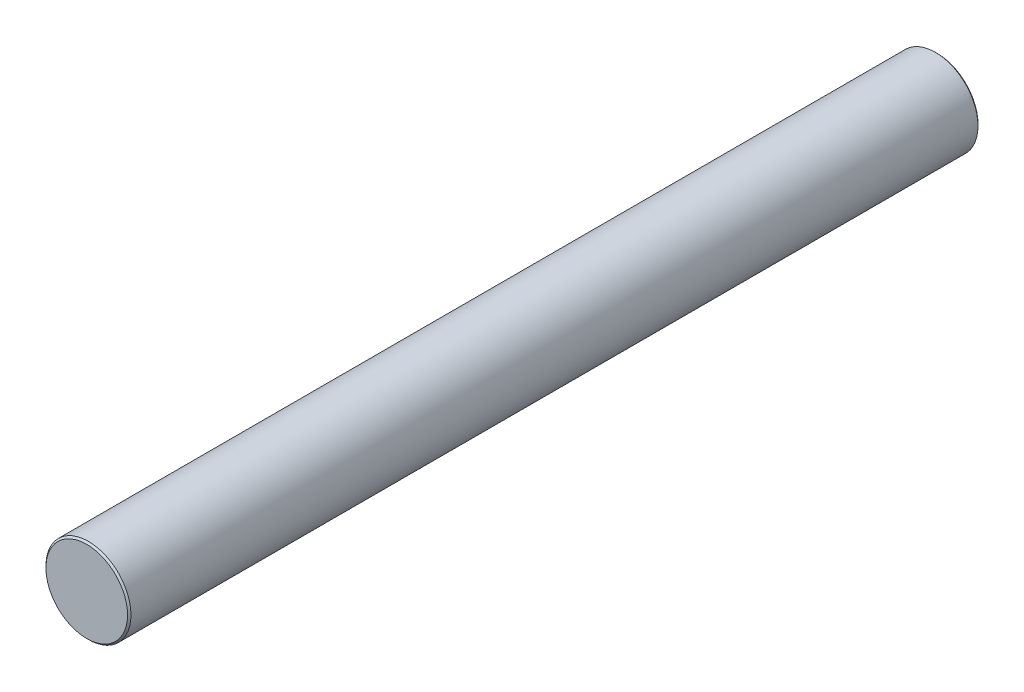
SolidWorks part; units mm, degrees
material "AISI 1045 Steel, cold drawn"
ref_plane "Front Plane" through (0, 0, 0) normal (0, 0, 1) x (1, 0, 0)
ref_plane "Top Plane" through (0, 0, 0) normal (0, 1, 0) x (1, 0, 0)
ref_plane "Right Plane" through (0, 0, 0) normal (1, 0, 0) x (0, 0, -1)
sketch "Sketch1" plane through (0, 0, 0) normal (0, 0, 1) x (1, 0, 0)
  line L1 (-2.3813, 3.9687) -> (2.3812, 3.9687)
  line L2 (-2.3813, 3.9687) -> (-2.3813, 8.7312)
  line L3 (-2.3813, 8.7312) -> (2.3812, 8.7312)
  line L4 (2.3812, 3.9687) -> (2.3812, 8.7312)
  line L5 (-2.3813, 3.9687) -> (2.3812, 8.7312) construction
  line L6 (-2.3813, 8.7312) -> (2.3812, 3.9687) construction
  circle A0 centre (0, 0) radius 6.35
  point P3 (0, 6.35)
  dimension "D1" = 12.7
  dimension "D2" = 4.7625
  dimension "D3" = 4.7625
extrude "Boss-Extrude1" add sketch "Sketch1" along normal blind 127 contours L2 A0 L4 L1 | L4 A0 L2 L1 region at (0, 5.0875, 0) region at (0, -0.4654, 0)
chamfer "Chamfer1" distance 0.254 angle 45 2 edges at (6.35, 0, 0) (6.35, 0, 127)
ref_axis "Axis1" through (0, 0, 126.746) along (0, 0, -1)
